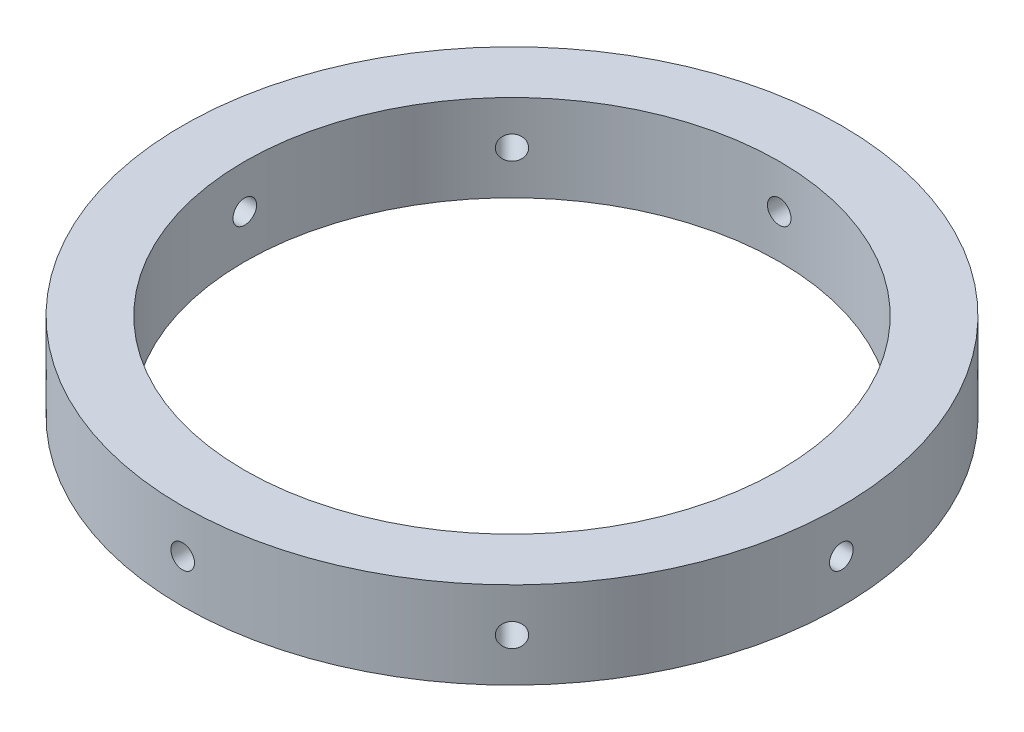
SolidWorks part; units mm, degrees
ref_plane "Front Plane" through (0, 0, 0) normal (0, 0, 1) x (1, 0, 0)
ref_plane "Top Plane" through (0, 0, 0) normal (0, 1, 0) x (1, 0, 0)
ref_plane "Right Plane" through (0, 0, 0) normal (1, 0, 0) x (0, 0, -1)
sketch "Sketch3" plane through (0, 0, 0) normal (0, 1, 0) x (1, 0, 0)
  circle A0 centre (0, 0) radius 53.1
  circle A1 centre (0, 0) radius 43.1
  dimension "D1" = 106.2
  dimension "D2" = 86.2
extrude "Boss-Extrude1" add sketch "Sketch3" along normal blind 14
ref_plane "Plane2" through (53.1, 0, 0) normal (1, 0, 0) x (0, 0, -1)
sketch "Sketch5" plane through (53.1, 0, 0) normal (1, 0, 0) x (0, 0, -1)
  line L0 (0, 0) -> (0, 14) construction
  line L1 (43.1, 14) -> (-43.1, 14) construction
  line L2 (-55.8566, 10) -> (-56.1948, 10) construction
  line L3 (-56.1948, 10) -> (55.6312, 10) construction
  circle A0 centre (0, 7) radius 1.9
  dimension "D1" = 3.8
extrude "Cut-Extrude1" cut sketch "Sketch5" against normal up to next
pattern_circular "CirPattern1" count 8 over 360 about axis through (0, 14, 0) along (0, -1, 0) of "Cut-Extrude1" reverse direction yes
equation "\"circulo grande\"= 106.2mm"
equation "\"D1@Sketch3\"=\"circulo grande\""
equation "\"circulo pequeño\"= 86.20mm"
equation "\"D2@Sketch3\"=\"circulo pequeño\""
equation "\"ancho\" = 1.4cm"
equation "\"Boss-Extrude1@Boss-Extrude1\"=\"ancho\""
equation "\"circulo tornillo\"= 3.8mm"
equation "\"D1@Sketch5\"=\"circulo tornillo\""
